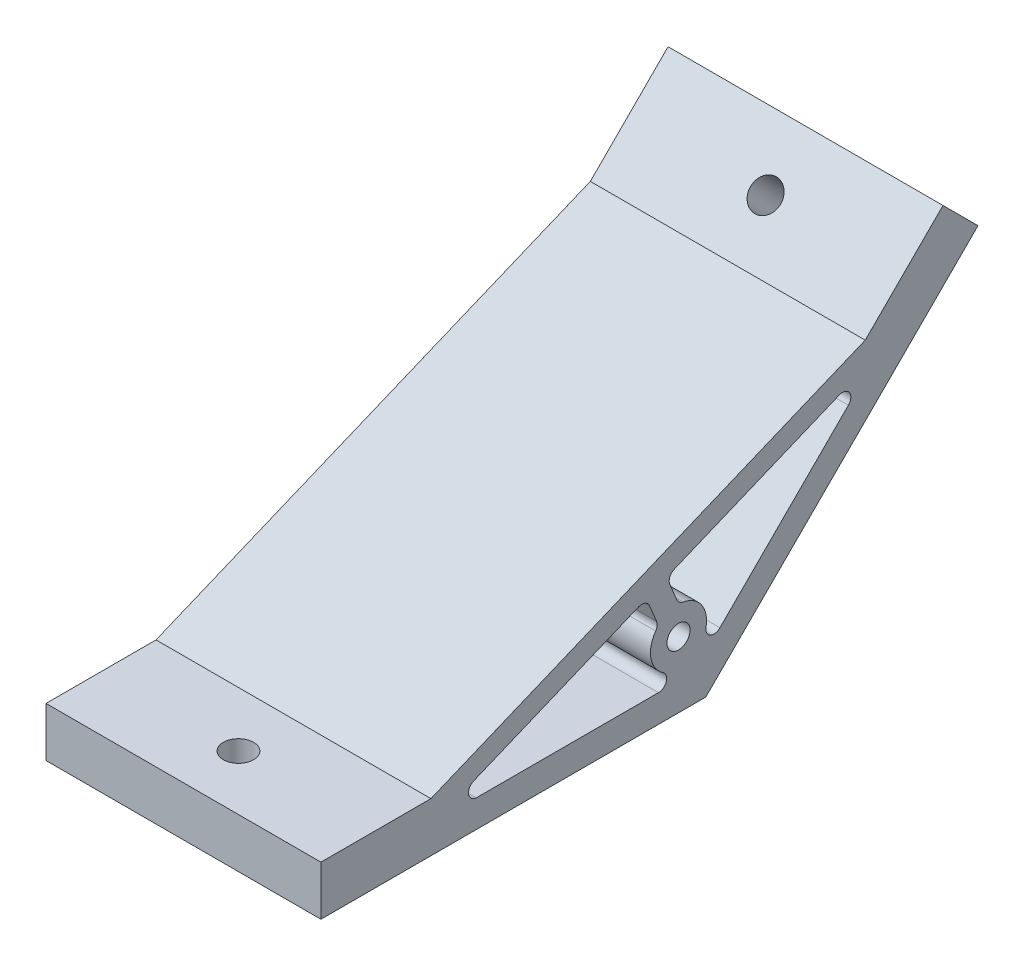
SolidWorks part; units mm, degrees
ref_plane "Front Plane" through (0, 0, 0) normal (0, 0, 1) x (1, 0, 0)
ref_plane "Top Plane" through (0, 0, 0) normal (0, 1, 0) x (1, 0, 0)
ref_plane "Right Plane" through (0, 0, 0) normal (1, 0, 0) x (0, 0, -1)
ref_plane "Plane1" through (7, 0, 0) normal (1, 0, 0) x (0, 0, -1)
sketch "Sketch1" plane through (7, 0, 0) normal (1, 0, 0) x (0, 0, -1)
  line L0 (-70, 9) -> (-70, 0)
  line L1 (-70, 0) -> (0, 0)
  line L2 (0, 0) -> (49.4975, 49.4975)
  line L3 (49.4975, 49.4975) -> (43.1335, 55.8614)
  line L4 (43.1335, 55.8614) -> (28.9914, 41.7193)
  line L5 (28.9914, 41.7193) -> (-49.9914, 9)
  line L6 (-49.9914, 9) -> (-70, 9)
extrude "Boss-Extrude1" add sketch "Sketch1" against normal blind 25 and the other way blind 25
sketch "Sketch2" plane through (32, 0, 0) normal (1, 0, 0) x (0, 0, -1)
  line L0 (-41.7559, 5.0029) -> (-8.6189, 5)
  line L1 (-8.6142, 15.5688) -> (-10.82, 20.8956)
  line L2 (-10.82, 20.8956) -> (-42.2372, 7.8859)
  arc A0 (-42.2372, 7.8859) -> (-41.7559, 5.0029) centre (-41.6633, 6.5) ccw
  arc A1 (-8.6189, 5) -> (-7.7993, 7.7564) centre (-8.6188, 6.5) ccw
  arc A2 (-7.7993, 7.7564) -> (-8.6142, 15.5688) centre (-4.9708, 12.0001) cw
extrude "Cut-Extrude1" cut sketch "Sketch2" against normal through all
sketch "Sketch3" plane through (-18, 0, 0) normal (-1, 0, 0) x (0, 0, 1)
  line L0 (-25.9249, 32.996) -> (-2.5589, 9.63)
  line L1 (4.9182, 17.0997) -> (7.1258, 22.4295)
  line L2 (7.1258, 22.4295) -> (-24.2902, 35.4424)
  arc A0 (-24.2902, 35.4424) -> (-25.9249, 32.996) centre (-24.8642, 34.0566) ccw
  arc A1 (-2.5589, 9.63) -> (-0.0281, 10.9882) centre (-1.4983, 10.6906) ccw
  arc A2 (-0.0281, 10.9882) -> (4.9182, 17.0997) centre (4.9706, 12) cw
extrude "Cut-Extrude2" cut sketch "Sketch3" against normal through all
hole_wizard "Ø5.5 (5.5) Diameter Hole1" positions "Sketch5" profile "Sketch4" hole size "Ø5.5" standard "ANSI Metric"
sketch "Sketch5" plane through (0, 0, 0) normal (0, -0.7071, -0.7071) x (-1, 0, 0)
  line L0 (18, 70) -> (18, 50) construction
  point P0 (-7, 59.7303)
  point P1 (0, 0)
  point P2 (-6.0217, 59.7303)
  point P3 (0, 0)
  point P4 (0, 0)
  dimension "D1" = 25
sketch "Sketch4" plane through (7, 42.2357, -42.2357) normal (1, 0, 0) x (0, 0.7071, -0.7071)
  line L0 (0, 0) -> (0, 88.9975)
  line L1 (0, 88.9975) -> (2.75, 88.9975)
  line L2 (2.75, 88.9975) -> (2.75, 0)
  line L5 (2.75, 0) -> (0, 0)
  line L11 (0, -6.35) -> (0, 107.95) construction
  dimension "Thru Hole Dia." = 5.5
  dimension "Thru Hole Depth" = 88.9975
hole_wizard "Ø5.5 (5.5) Diameter Hole2" positions "Sketch7" profile "Sketch6" hole size "Ø5.5" standard "ANSI Metric"
sketch "Sketch7" plane through (0, 0, 0) normal (0, -1, 0) x (-1, 0, 0)
  line L0 (18, -49.9914) -> (18, -70) construction
  point P0 (-7, -60)
  dimension "D1" = 25
sketch "Sketch6" plane through (7, 0, 60) normal (1, 0, 0) x (0, 0, -1)
  line L0 (0, 0) -> (0, 55.8614)
  line L1 (0, 55.8614) -> (2.75, 55.8614)
  line L2 (2.75, 55.8614) -> (2.75, 0)
  line L5 (2.75, 0) -> (0, 0)
  line L11 (0, -6.35) -> (0, 107.95) construction
  dimension "Thru Hole Dia." = 5.5
  dimension "Thru Hole Depth" = 55.8614
hole_wizard "Ø4.2 (4.2) Diameter Hole1" positions "Sketch9" profile "Sketch8" hole size "Ø4.2" standard "ANSI Metric"
sketch "Sketch9" plane through (-18, 0, 0) normal (-1, 0, 0) x (0, 0, 1)
  point P0 (4.9706, 12)
sketch "Sketch8" plane through (-18, 12, 4.9706) normal (0, 1, 0) x (0, 0, 1)
  line L0 (0, 0) -> (0, 50)
  line L1 (0, 50) -> (2.1, 50)
  line L2 (2.1, 50) -> (2.1, 0)
  line L5 (2.1, 0) -> (0, 0)
  line L11 (0, -6.35) -> (0, 107.95) construction
  dimension "Thru Hole Dia." = 4.2
  dimension "Thru Hole Depth" = 50
fillet "Fillet1" radius 1.5 4 edges at (7, 15.5688, 8.6142) (7, 22.4295, 7.1258) (7, 20.8956, 10.82) (7, 17.0997, 4.9182) tangent propagation no
ref_point "Point1"
